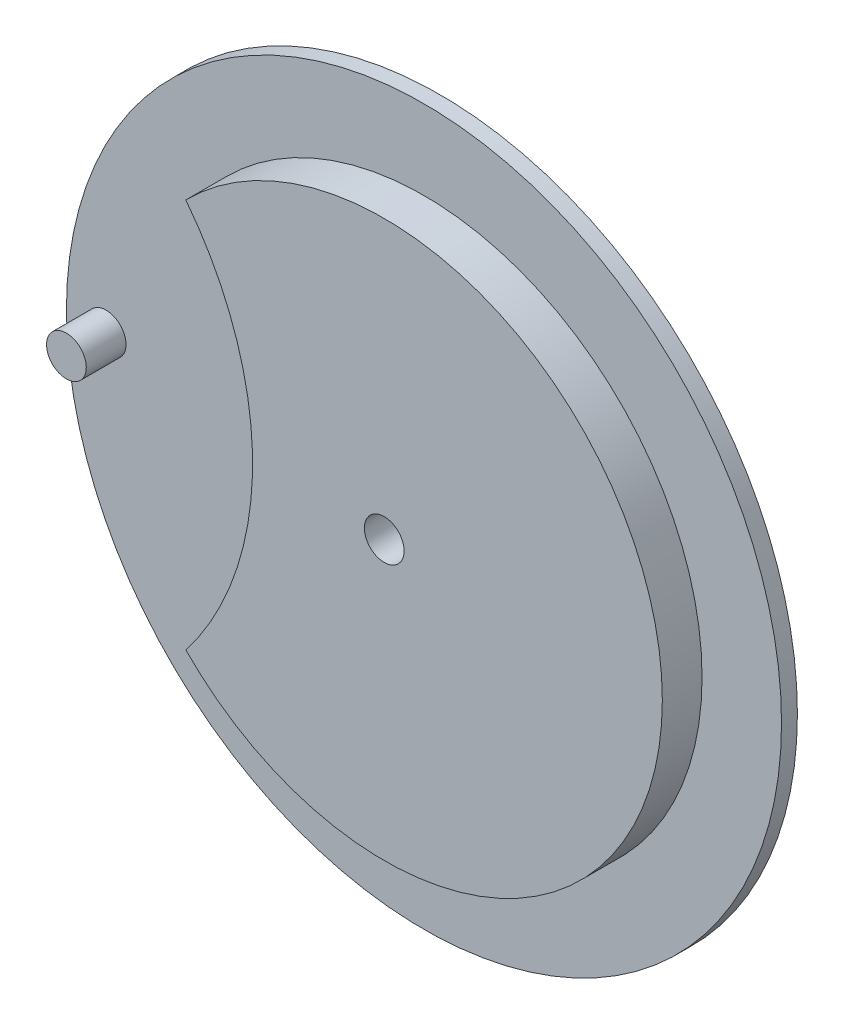
SolidWorks part; units mm, degrees
ref_plane "前视基准面" through (0, 0, 0) normal (0, 0, 1) x (1, 0, 0)
ref_plane "上视基准面" through (0, 0, 0) normal (0, 1, 0) x (1, 0, 0)
ref_plane "右视基准面" through (0, 0, 0) normal (1, 0, 0) x (0, 0, -1)
other "Configuration Table"
sketch "草图1" plane through (0, 0, 0) normal (0, 0, 1) x (1, 0, 0)
  line L0 (-2.5297, 2.5297) -> (-3.6261, 3.6261) construction
  line L1 (0, 0) -> (-1.9675, 1.9675) construction
  circle A0 centre (0, 0) radius 0.1987
  circle A1 centre (0, 0) radius 3.5775
  arc A3 (-1.9851, -1.9498) -> (-1.9851, 1.9498) centre (0, 0) ccw
  circle A4 centre (-3.18, 0) radius 0.1988
  arc A5 (-1.9851, -1.9498) -> (-1.9851, 1.9498) centre (-4.4972, 0) ccw
  dimension "D2" = 0.3975
  dimension "D5" = 0.3975
extrude "凸台-拉伸2" add sketch "草图1" against normal blind 0.159 contours A5 A3 A0 | A1 A4 A3 A5 | A4 region at (-3.4763, 0, 0) region at (0.3939, 0, 0) region at (-3.18, 0, 0)
extrude "凸台-拉伸3" add sketch "草图1<6>" along normal blind 0.3975 contours A5 A3 A0 | A4 region at (0.3939, 0, 0) region at (-3.18, 0, 0)
sketch "草图1<6>" plane through (0, 0, 0) normal (0, 0, 1) x (1, 0, 0) same geometry as "草图1"
